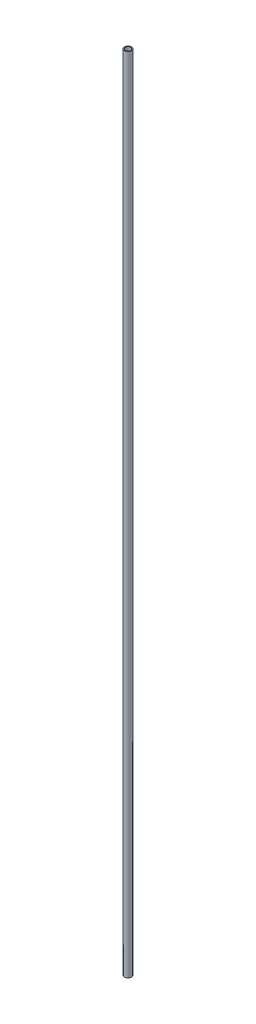
SolidWorks part; units mm, degrees
material "PVC Rigid"
ref_plane "Front Plane" through (0, 0, 0) normal (0, 0, 1) x (1, 0, 0)
ref_plane "Top Plane" through (0, 0, 0) normal (0, 1, 0) x (1, 0, 0)
ref_plane "Right Plane" through (0, 0, 0) normal (1, 0, 0) x (0, 0, -1)
sketch "Sketch1" plane through (0, 0, 0) normal (0, 1, 0) x (1, 0, 0)
  circle A0 centre (0, 0) radius 10.2108
  circle A1 centre (0, 0) radius 13.335
  dimension "D1" = 26.67
  dimension "D2" = 20.4216
extrude "Boss-Extrude1" add sketch "Sketch1" along normal blind 3048
